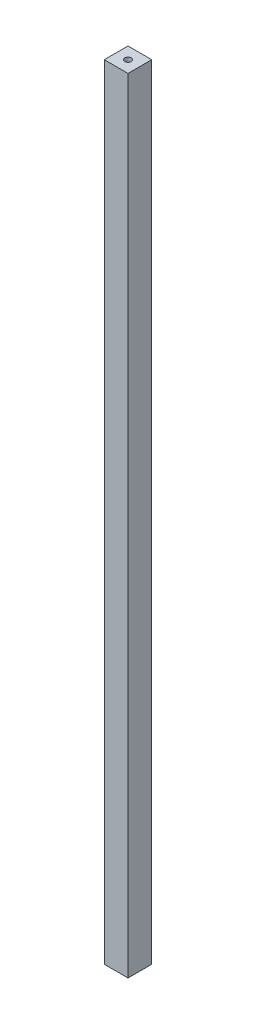
SolidWorks part; units mm, degrees
ref_plane "Front Plane" through (0, 0, 0) normal (0, 0, 1) x (1, 0, 0)
ref_plane "Top Plane" through (0, 0, 0) normal (0, 1, 0) x (1, 0, 0)
ref_plane "Right Plane" through (0, 0, 0) normal (1, 0, 0) x (0, 0, -1)
sketch "Sketch1" plane through (0, 0, 0) normal (0, 1, 0) x (1, 0, 0)
  line L1 (0, 0) -> (10, 0)
  line L2 (0, 0) -> (0, 10)
  line L3 (0, 10) -> (10, 10)
  line L4 (10, 0) -> (10, 10)
  dimension "D1" = 10
extrude "Boss-Extrude1" add sketch "Sketch1" along normal blind 330
hole_wizard "#6-32 Tapped Hole1" positions "Sketch2" profile "Sketch3" tap size "#6-32" standard "ANSI Inch" end condition through all
sketch "Sketch2" plane through (0, 330, 0) normal (0, 1, 0) x (1, 0, 0)
  line L0 (0, 10) -> (10, 0) construction
  line L2 (10, 10) -> (0, 0) construction
  point P13 (5, 5)
sketch "Sketch3" plane through (5, 330, -5) normal (1, 0, 0) x (0, 0, 1)
  line L0 (0, 0) -> (0, 330)
  line L1 (0, 330) -> (1.3525, 330)
  line L2 (1.3525, 330) -> (1.3525, 0)
  line L5 (1.3525, 0) -> (0, 0)
  line L11 (0, -6.35) -> (0, 107.95) construction
  dimension "Thread Major Dia." = 2.7051
  dimension "Thru Tap Drill Depth" = 330
